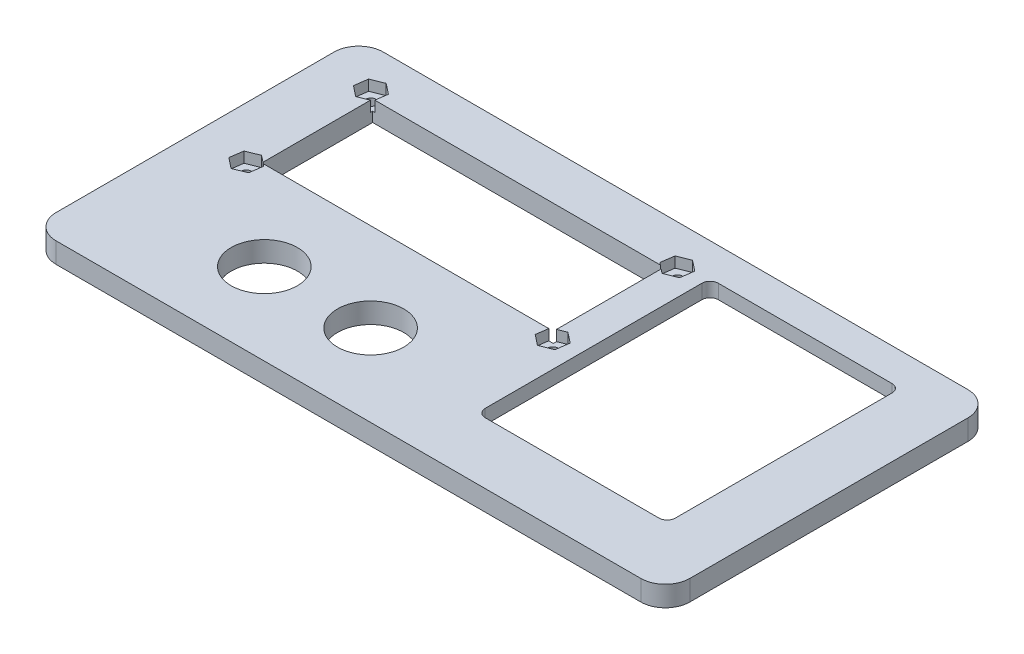
SolidWorks part; units mm, degrees
ref_plane "Front Plane" through (0, 0, 0) normal (0, 0, 1) x (1, 0, 0)
ref_plane "Top Plane" through (0, 0, 0) normal (0, 1, 0) x (1, 0, 0)
ref_plane "Right Plane" through (0, 0, 0) normal (1, 0, 0) x (0, 0, -1)
sketch "Sketch1" plane through (0, 0, 0) normal (0, 1, 0) x (1, 0, 0)
  line L1 (-77.5, -40) -> (77.5, -40)
  line L2 (-77.5, -40) -> (-77.5, 40)
  line L3 (-77.5, 40) -> (77.5, 40)
  line L4 (77.5, -40) -> (77.5, 40)
  line L5 (-77.5, -40) -> (77.5, 40) construction
  line L6 (-77.5, 40) -> (77.5, -40) construction
  point P0 (0, 0)
  dimension "D1" = 155
  dimension "D2" = 80
extrude "Boss-Extrude1" add sketch "Sketch1" along normal blind 5
sketch "Sketch2" plane through (0, 5, 0) normal (0, 1, 0) x (1, 0, 0)
  line L1 (-62.8518, 1.6691) -> (8.446, 1.6691)
  line L2 (-62.8518, 1.6691) -> (-62.8518, 28.7709)
  line L3 (-62.8518, 28.7709) -> (8.446, 28.7709)
  line L4 (8.446, 1.6691) -> (8.446, 28.7709)
  line L5 (-62.8518, 1.6691) -> (8.446, 28.7709) construction
  line L6 (-62.8518, 28.7709) -> (8.446, 1.6691) construction
  line L7 (-67.5, 15.22) -> (12.51, 15.22) construction
  line L8 (-67.5, 33) -> (12.51, 33) construction
  line L9 (-67.5, 33) -> (-67.5, -2.56) construction
  line L10 (-67.5, -2.56) -> (12.51, -2.56) construction
  line L11 (12.51, 33) -> (12.51, -2.56) construction
  line L12 (77.5, 40) -> (-77.5, 40) construction
  line L13 (-77.5, 40) -> (-77.5, -40) construction
  circle A0 centre (-64.96, -0.02) radius 1.27
  circle A1 centre (9.97, -0.02) radius 1.27
  circle A2 centre (9.97, 30.46) radius 1.27
  circle A3 centre (-64.96, 30.46) radius 1.27
  point P0 (-27.2029, 15.22)
  point P6 (-27.2029, 17.22)
  point P20 (-27.495, 15.22)
  dimension "D7" = 2.54
  dimension "D8" = 2.54
  dimension "D1" = 71.2978
  dimension "D2" = 27.1018
  dimension "D3" = 7
  dimension "D4" = 35.56
  dimension "D5" = 80.01
  dimension "D6" = 4.6482
  dimension "D9" = 33.02
  dimension "D10" = 77.47
  dimension "D11" = 5.08
  dimension "D12" = 10
extrude "Screen Cutout" cut sketch "Sketch2" against normal through all
sketch "Sketch8" plane through (0, 5, 0) normal (0, 1, 0) x (1, 0, 0)
  line L1 (-68.0135, 29.2327) -> (-65.4238, 27.202)
  line L2 (-65.4238, 27.202) -> (-62.3704, 28.4293)
  line L3 (-62.3704, 28.4293) -> (-61.9065, 31.6873)
  line L4 (-61.9065, 31.6873) -> (-64.4962, 33.718)
  line L5 (-64.4962, 33.718) -> (-67.5496, 32.4907)
  line L6 (-67.5496, 32.4907) -> (-68.0135, 29.2327)
  line L7 (6.9165, 29.2327) -> (9.5062, 27.202)
  line L8 (9.5062, 27.202) -> (12.5596, 28.4293)
  line L9 (12.5596, 28.4293) -> (13.0235, 31.6873)
  line L10 (13.0235, 31.6873) -> (10.4338, 33.718)
  line L11 (10.4338, 33.718) -> (7.3804, 32.4907)
  line L12 (7.3804, 32.4907) -> (6.9165, 29.2327)
  line L13 (6.9165, -1.2473) -> (9.5062, -3.278)
  line L14 (9.5062, -3.278) -> (12.5596, -2.0507)
  line L15 (12.5596, -2.0507) -> (13.0235, 1.2073)
  line L16 (13.0235, 1.2073) -> (10.4338, 3.238)
  line L17 (10.4338, 3.238) -> (7.3804, 2.0107)
  line L18 (7.3804, 2.0107) -> (6.9165, -1.2473)
  line L19 (-68.0135, -1.2473) -> (-65.4238, -3.278)
  line L20 (-65.4238, -3.278) -> (-62.3704, -2.0507)
  line L21 (-62.3704, -2.0507) -> (-61.9065, 1.2073)
  line L22 (-61.9065, 1.2073) -> (-64.4962, 3.238)
  line L23 (-64.4962, 3.238) -> (-67.5496, 2.0107)
  line L24 (-67.5496, 2.0107) -> (-68.0135, -1.2473)
  circle A0 centre (-64.96, 30.46) radius 2.85 construction
  circle A1 centre (9.97, 30.46) radius 2.85 construction
  circle A2 centre (9.97, -0.02) radius 2.85 construction
  circle A3 centre (-64.96, -0.02) radius 2.85 construction
  dimension "D1" = 5.7
extrude "Screen hex nuts" cut sketch "Sketch8" against normal blind 2.6
sketch "Sketch3" plane through (0, 0, 0) normal (0, 1, 0) x (1, 0, 0)
  line L0 (-40.5818, -20) -> (-14.5818, -20) construction
  line L1 (-48.7318, -11.45) -> (-48.7318, -28.55) construction
  line L2 (-48.7318, -28.55) -> (-6.4318, -28.55) construction
  line L3 (-62.4954, 1.6691) -> (7.3317, 1.6691) construction
  line L4 (-77.5, -40) -> (77.5, -40) construction
  line L7 (-27.5818, 26.9252) -> (-27.5818, -22.8987) construction
  circle A0 centre (-40.5818, -20) radius 8.1
  circle A1 centre (-14.5818, -20) radius 8.1
  circle A2 centre (-48.7318, -11.45) radius 1.1906
  circle A3 centre (-6.4318, -11.45) radius 1.1906
  circle A4 centre (-6.4318, -28.55) radius 1.1906
  circle A5 centre (-48.7318, -28.55) radius 1.1906
  point P4 (-27.5818, -28.55)
  point P14 (-27.5818, -20)
  point P19 (-27.5818, 1.6691)
  dimension "D1" = 16.2
  dimension "D2" = 26
  dimension "D3" = 2.3813
  dimension "D4" = 17.1
  dimension "D5" = 20
  dimension "D6" = 42.3
  dimension "D7" = 8.55
extrude "Ultrasound Cutouts" cut sketch "Sketch3" along normal through all contours A1 | A0
extrude "Cut-Extrude2" cut sketch "Sketch3<3>" along normal blind 3.175
sketch "Sketch3<3>" plane through (0, 0, 0) normal (0, 1, 0) x (1, 0, 0) same geometry as "Sketch3"
sketch "Sketch4" plane through (0, 5, 0) normal (0, 1, 0) x (1, 0, 0)
  circle A0 centre (-21.6513, -28.8183) radius 0.85
  circle A1 centre (20.3487, -11.8183) radius 0.85
  circle A2 centre (-21.6513, -11.8183) radius 0.85
  circle A3 centre (20.3487, -28.8183) radius 0.85
  dimension "D1" = 1.7
  dimension "D2" = 17
  dimension "D3" = 42
extrude "Ultrasound Bolt Holes" [suppressed] cut sketch "Sketch4" against normal through all
sketch "Sketch5" plane through (0, 0, 0) normal (0, -1, 0) x (1, 0, 0)
  line L0 (-6.322, 30.05) -> (-48.622, 30.05) construction
  line L1 (-21.472, 30.05) -> (-33.472, 30.05)
  line L2 (-21.472, 30.05) -> (-21.472, 25.05)
  line L3 (-21.472, 25.05) -> (-33.472, 25.05)
  line L4 (-33.472, 30.05) -> (-33.472, 25.05)
  line L5 (-21.472, 30.05) -> (-33.472, 25.05) construction
  line L6 (-21.472, 25.05) -> (-33.472, 30.05) construction
  circle A1 centre (-6.4318, 28.55) radius 1.1906 construction
  point P0 (-27.472, 27.55)
  point P13 (-27.472, 30.05)
  point P14 (-27.472, 30.05)
  dimension "D3" = 1.5
  dimension "D1" = 12
  dimension "D2" = 5
extrude "US Clock cutout" cut sketch "Sketch5" against normal blind 4
sketch "Sketch6" plane through (0, 0, 0) normal (0, -1, 0) x (1, 0, 0)
  line L0 (-21.472, 27.55) -> (-33.472, 27.55) construction
  line L1 (-22.472, 13.3) -> (-32.472, 13.3)
  line L2 (-22.472, 13.3) -> (-22.472, 9.8)
  line L3 (-22.472, 9.8) -> (-32.472, 9.8)
  line L4 (-32.472, 13.3) -> (-32.472, 9.8)
  line L5 (-22.472, 13.3) -> (-32.472, 9.8) construction
  line L6 (-22.472, 9.8) -> (-32.472, 13.3) construction
  line L7 (-21.472, 25.05) -> (-21.472, 30.05) construction
  line L8 (-33.472, 30.05) -> (-33.472, 25.05) construction
  line L9 (-6.6073, 10.2724) -> (-48.9073, 10.2724) construction
  line L10 (-27.472, 5.8213) -> (-27.472, 1.0358) construction
  point P0 (-27.472, 11.55)
  point P19 (0, 0)
  point P20 (-27.472, 27.55)
  dimension "D1" = 10
  dimension "D2" = 3.5
  dimension "D3" = 16
extrude "US Pin cutout" cut sketch "Sketch6" against normal blind 2
fillet "Fillet2" [suppressed] radius 1
ref_plane "Magnet plane" through (0, 0.2, 0) normal (0, -1, 0) x (-1, 0, 0)
sketch "Sketch9" plane through (0, 0.2, 0) normal (0, -1, 0) x (-1, 0, 0)
  line L0 (-77.5, -40) -> (-77.5, 40) construction
  line L1 (-77.5, 40) -> (77.5, 40) construction
  line L2 (77.5, -40) -> (-77.5, -40) construction
  line L3 (77.5, 40) -> (77.5, -40) construction
  circle A0 centre (-71.5, 34) radius 3.15
  circle A1 centre (71.5, 34) radius 3.15
  circle A2 centre (-71.5, -34) radius 3.15
  circle A3 centre (71.5, -34) radius 3.15
  dimension "D1" = 6.3
  dimension "D2" = 6
  dimension "D3" = 6
  dimension "D4" = 6
  dimension "D5" = 6
extrude "Magnet Holes" cut sketch "Sketch9" against normal blind 2.1
fillet "Fillet1" radius 6 4 edges at (77.5, 2.5, -40) (77.5, 2.5, 40) (-77.5, 2.5, 40) (-77.5, 2.5, -40)
sketch "Sketch10" plane through (0, 5, 0) normal (0, 1, 0) x (1, 0, 0)
  line L0 (8.446, 2.439) -> (8.446, 28.0333) construction
  line L1 (16.446, -25) -> (62.946, -25)
  line L2 (16.446, -25) -> (16.446, 32)
  line L3 (16.446, 32) -> (62.946, 32)
  line L4 (62.946, -25) -> (62.946, 32)
  line L5 (16.446, -25) -> (62.946, 32) construction
  line L6 (16.446, 32) -> (62.946, -25) construction
  line L7 (71.5, 40) -> (-71.5, 40) construction
  point P0 (39.696, 3.5)
  dimension "D1" = 46.5
  dimension "D2" = 57
  dimension "D3" = 8
  dimension "D4" = 8
extrude "Keypad cutout" cut sketch "Sketch10" against normal through all
sketch "Sketch11" plane through (0, 0, 0) normal (0, -1, 0) x (1, 0, 0)
  line L0 (58.696, 34.5) -> (58.696, 28.5)
  line L1 (65.696, -35.5) -> (13.696, -35.5)
  line L2 (65.696, -35.5) -> (65.696, 28.5)
  line L3 (65.696, 28.5) -> (13.696, 28.5)
  line L4 (13.696, -35.5) -> (13.696, 28.5)
  line L5 (58.696, 34.5) -> (20.696, 34.5)
  line L6 (58.696, 28.5) -> (20.696, 28.5)
  line L7 (20.696, 34.5) -> (20.696, 28.5)
  line L8 (58.696, 34.5) -> (20.696, 28.5) construction
  line L9 (58.696, 28.5) -> (20.696, 34.5) construction
  line L10 (62.946, -32) -> (16.446, 25) construction
  line L11 (16.446, -32) -> (62.946, 25) construction
  line L12 (39.696, 25.3529) -> (39.696, -31.6471) construction
  line L14 (62.946, -3.5) -> (16.446, -3.5) construction
  point P4 (39.696, 28.5)
  point P5 (39.696, 31.5)
  point P6 (39.696, 28.5)
  point P16 (39.696, -35.5)
  point P23 (65.696, -3.5)
  point P24 (39.696, -3.5)
  line M12 (62.946, 25) -> (62.946, -32)
  line M13 (62.946, -32) -> (16.446, -32)
  line M14 (16.446, -32) -> (16.446, 25)
  line M15 (16.446, 25) -> (62.946, 25)
  dimension "D1" = 52
  dimension "D2" = 64
  dimension "D3" = 38
  dimension "D4" = 6
extrude "Cut-Extrude1" cut sketch "Sketch11" against normal blind 1.5 contours M12 M15 M14 M13 | L4 L1 L2 L3 M15 M12 M13 M14 | L5 L7 L3 L0 region at (39.696, 0, 31.5) region at (62.196, 0, 27.6754) region at (39.696, 0, -3.5)
fillet "Fillet3" radius 2 4 edges at (65.696, 0.75, 28.5) (13.696, 0.75, 28.5) (13.696, 0.75, -35.5) (65.696, 0.75, -35.5)
fillet "Fillet4" radius 2 4 edges at (62.946, 3.25, 25) (16.446, 3.25, 25) (16.446, 3.25, -32) (62.946, 3.25, -32)
sketch "Sketch12" plane through (0, 1.5, 0) normal (0, -1, 0) x (1, 0, 0)
  circle A0 centre (63.092, -34.1237) radius 1.5
  circle A1 centre (15.8391, -34.1237) radius 1.5
  circle A2 centre (15.8391, 26.403) radius 1.5
  circle A3 centre (63.092, 26.403) radius 1.5
  point P8 (0, 0)
  point P9 (0, 0)
  point P10 (0, 0)
  point P11 (0, 0)
  point P12 (17.0318, 23)
  point P13 (15.8391, 26.403)
  dimension "D1" = 3
extrude "Cut-Extrude3" cut sketch "Sketch12" against normal blind 2.9
